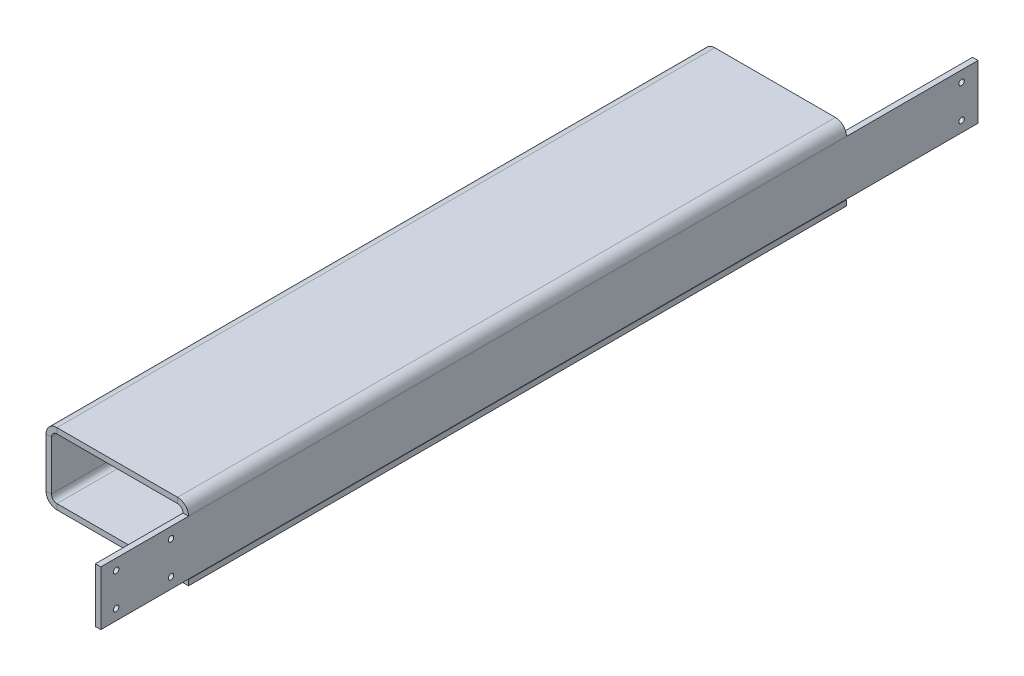
SolidWorks part; units mm, degrees
note: The reader was unsure of these and kept them because the rebuilt part matched: flange length of "Edge-Flange1", "Edge-Flange2", "Edge-Flange3".
ref_plane "Front Plane" through (0, 0, 0) normal (0, 0, 1) x (1, 0, 0)
ref_plane "Top Plane" through (0, 0, 0) normal (0, 1, 0) x (1, 0, 0)
ref_plane "Right Plane" through (0, 0, 0) normal (1, 0, 0) x (0, 0, -1)
sketch "Sketch1" plane through (0, 0, 0) normal (0, 1, 0) x (1, 0, 0)
  line L1 (0, 0) -> (79.375, 0)
  line L2 (0, 0) -> (0, 381)
  line L3 (0, 381) -> (79.375, 381)
  line L4 (79.375, 0) -> (79.375, 381)
  dimension "D1" = 79.375
  dimension "D2" = 381
base flange "Base-Flange1" sketch "Sketch1" thickness 3.175 reverse thickness direction no parameters "D1"=3.175
edge flange "Edge-Flange1" sketch "Sketch8" flange angle 90 flange length 38.1 flange position material outside bend radius 3.175 thickness 3.175 relief rectangular parameters "D6"=10
sketch "Sketch8" plane through (0, 0, 0) normal (-1, 0, 0) x (0, 0, 1)
  line L0 (-381, 0) -> (0, 0) construction
  line L1 (-381, 0) -> (0, 0)
  line L2 (-381, 0) -> (-381, 34.925)
  line L3 (-381, 34.925) -> (0, 34.925)
  line L4 (0, 34.925) -> (0, 0)
bend "EdgeBend1" bend radius 3.175 bend angle 90 parameters "D5"=1
edge flange "Edge-Flange2" sketch "Sketch13" flange angle 90 flange length 79.375 flange position material outside bend radius 3.175 thickness 3.175 relief rectangular parameters "D6"=10
sketch "Sketch13" plane through (0, 34.925, 0) normal (0, 1, 0) x (0, 0, 1)
  line L2 (0, 0) -> (0, 76.2)
  line L3 (0, 76.2) -> (-381, 76.2)
  line L4 (-381, 76.2) -> (-381, 0)
  line L6 (0, 0) -> (-381, 0) construction
  line L7 (0, 0) -> (-381, 0)
bend "EdgeBend2" bend radius 3.175 bend angle 90 parameters "D5"=2
edge flange "Edge-Flange3" sketch "Sketch16" flange angle 90 flange length 37.846 flange position material outside bend radius 3.175 thickness 3.175 relief rectangular parameters "D6"=10
sketch "Sketch16" plane through (76.2, 34.925, 0) normal (1, 0, 0) x (0, 0, 1)
  line L0 (0, 0) -> (-381, 0) construction
  line L1 (0, 0) -> (-381, 0)
  line L2 (-381, 0) -> (-381, 34.671)
  line L3 (-381, 34.671) -> (0, 34.671)
  line L4 (0, 34.671) -> (0, 0)
bend "EdgeBend3" bend radius 3.175 bend angle 90 parameters "D5"=3
sketch "Sketch17" plane through (0, 0, 0) normal (0, 1, 0) x (1, 0, 0)
  line L1 (3.175, 381) -> (76.2, 381)
  line L2 (3.175, 381) -> (3.175, 457.2)
  line L3 (3.175, 457.2) -> (76.2, 457.2)
  line L4 (76.2, 381) -> (76.2, 457.2)
  line L5 (79.375, 381) -> (76.2, 381) construction
  dimension "D1" = 3.175
  dimension "D2" = 76.2
sketch "Sketch20" plane through (0, 0, 0) normal (0, 1, 0) x (1, 0, 0)
  line L0 (76.2, 0) -> (79.375, 0) construction
  line L1 (0, 0) -> (76.2, 0)
  line L2 (0, 0) -> (0, -50.8)
  line L3 (0, -50.8) -> (76.2, -50.8)
  line L4 (76.2, 0) -> (76.2, -50.8)
  line L5 (3.175, 0) -> (79.375, 0) construction
  point P8 (0, 0)
  dimension "D1" = 50.8
  dimension "D2" = 3.175
sketch "Sketch24" plane through (76.2, 0, 0) normal (-1, 0, 0) x (0, 0, 1)
  line L1 (0, 31.75) -> (50.8, 31.75)
  line L2 (0, 31.75) -> (0, 0.254)
  line L3 (0, 0.254) -> (50.8, 0.254)
  line L4 (50.8, 31.75) -> (50.8, 0.254)
  point P5 (0, 0)
  dimension "D1" = 50.8
base flange "Tab3" sketch "Sketch24" thickness 3.175 reverse thickness direction no parameters "D1"=3.175
sketch "Sketch27" plane through (76.2, 0, 0) normal (-1, 0, 0) x (0, 0, 1)
  line L1 (-381, 0.254) -> (-457.2, 0.254)
  line L2 (-381, 0.254) -> (-381, 31.75)
  line L3 (-381, 31.75) -> (-457.2, 31.75)
  line L4 (-457.2, 0.254) -> (-457.2, 31.75)
  point P5 (0, 0)
  dimension "D1" = 76.2
base flange "Tab4" sketch "Sketch27" thickness 3.175 reverse thickness direction no parameters "D1"=3.175
sketch "Sketch30" plane through (76.2, 0, 0) normal (-1, 0, 0) x (0, 0, 1)
  line L0 (50.8, 0.254) -> (50.8, 31.75) construction
  line L1 (10.16, 25.527) -> (41.91, 25.527) construction
  line L2 (10.16, 25.527) -> (10.16, 6.477) construction
  line L3 (10.16, 6.477) -> (41.91, 6.477) construction
  line L4 (41.91, 25.527) -> (41.91, 6.477) construction
  line L6 (41.91, 16.002) -> (50.8, 16.002) construction
  circle A0 centre (10.16, 25.527) radius 1.5875
  circle A1 centre (41.91, 25.527) radius 1.5875
  circle A2 centre (41.91, 6.477) radius 1.5875
  circle A3 centre (10.16, 6.477) radius 1.5875
  dimension "D1" = 3.175
  dimension "D2" = 8.89
  dimension "D4" = 31.75
  dimension "D5" = 19.05
extrude "Cut-Extrude2" cut sketch "Sketch30" against normal through all normal cut yes
sketch "Sketch31" plane through (76.2, 0, 0) normal (-1, 0, 0) x (0, 0, 1)
  line L0 (-447.675, 6.477) -> (-447.675, 25.527) construction
  line L1 (-447.675, 16.002) -> (-457.2, 16.002) construction
  line L2 (-457.2, 31.75) -> (-457.2, 0.254) construction
  circle A0 centre (-447.675, 25.527) radius 1.5875
  circle A1 centre (-447.675, 6.477) radius 1.5875
  dimension "D1" = 3.175
  dimension "D2" = 19.05
  dimension "D3" = 9.525
extrude "Cut-Extrude3" cut sketch "Sketch31" against normal through all normal cut yes
sketch "Bend-Lines1" [suppressed] plane through (0, 0, 0) normal (0, 1, 0) x (1, 0, 0)
sketch "Bounding-Box1" [suppressed] plane through (0, 0, 0) normal (0, 1, 0) x (1, 0, 0)
sheet metal parameters "Sheet-Metal1" thickness 3.175 parameters "D1"=3.175
flat pattern "Flat-Pattern1" [suppressed]
sketch "Bend-Lines2" plane through (0, 0, 0) normal (0, 1, 0) x (1, 0, 0)
sketch3d "Bounding-Box2" [suppressed]
  line L0 (0, 0, 0) -> (0, 381, 0) construction
  line L1 (79.375, 0, 0) -> (79.375, 381, 0) construction
  line L2 (0, 0, 0) -> (79.375, 0, 0) construction
  line L3 (0, 381, 0) -> (79.375, 381, 0) construction
sheet metal parameters "Sheet-Metal2" thickness 3.175 parameters "D1"=3.175
flat pattern "Flat-Pattern1"
sketch "Bend-Lines2" plane through (0, 0, 0) normal (0, 1, 0) x (1, 0, 0)
  line L0 (-0.5655, 381) -> (-0.5655, 0) construction
  line L1 (-0.5655, 381) -> (-0.5655, 0) construction
sketch3d "Bounding-Box2" [suppressed]
  line L0 (-36.0559, 0, 0) -> (-36.0559, 381, 0) construction
  line L1 (79.375, 0, 0) -> (79.375, 381, 0) construction
  line L2 (-36.0559, 0, 0) -> (79.375, 0, 0) construction
  line L3 (-36.0559, 381, 0) -> (79.375, 381, 0) construction
bend of the flat pattern "Flatten-<EdgeBend1>1"
sheet metal parameters "Sheet-Metal3" thickness 3.175 parameters "D1"=3.175
flat pattern "Flat-Pattern1"
sketch "Bend-Lines2" plane through (0, 0, 0) normal (0, 1, 0) x (1, 0, 0)
  line L0 (-0.5655, 381) -> (-0.5655, 0) construction
  line L1 (-0.5655, 381) -> (-0.5655, 0) construction
  line L2 (-36.6214, 381) -> (-36.6214, 0) construction
  line L3 (-36.6214, 381) -> (-36.6214, 0) construction
sketch3d "Bounding-Box2" [suppressed]
  line L0 (-113.3868, 0, 0) -> (-113.3868, 381, 0) construction
  line L1 (79.375, 0, 0) -> (79.375, 381, 0) construction
  line L2 (-113.3868, 0, 0) -> (79.375, 0, 0) construction
  line L3 (-113.3868, 381, 0) -> (79.375, 381, 0) construction
bend of the flat pattern "Flatten-<EdgeBend1>1"
bend of the flat pattern "Flatten-<EdgeBend2>1"
sheet metal parameters "Sheet-Metal4" thickness 3.175 parameters "D1"=3.175
flat pattern "Flat-Pattern1"
sketch "Bend-Lines2" plane through (0, 0, 0) normal (0, 1, 0) x (1, 0, 0)
  line L0 (-0.5655, 381) -> (-0.5655, 0) construction
  line L1 (-0.5655, 381) -> (-0.5655, 0) construction
  line L2 (-36.6214, 381) -> (-36.6214, 0) construction
  line L3 (-36.6214, 381) -> (-36.6214, 0) construction
  line L4 (-113.9523, 381) -> (-113.9523, 0) construction
  line L5 (-113.9523, 381) -> (-113.9523, 0) construction
sketch3d "Bounding-Box2" [suppressed]
  line L0 (-149.1888, 0, 0) -> (-149.1888, 381, 0) construction
  line L1 (79.375, 0, 0) -> (79.375, 381, 0) construction
  line L2 (-149.1888, 0, 0) -> (79.375, 0, 0) construction
  line L3 (-149.1888, 381, 0) -> (79.375, 381, 0) construction
bend of the flat pattern "Flatten-<EdgeBend1>1"
bend of the flat pattern "Flatten-<EdgeBend2>1"
bend of the flat pattern "Flatten-<EdgeBend3>1"
sheet metal parameters "Sheet-Metal8" thickness 3.175 parameters "D1"=3.175
flat pattern "Flat-Pattern8"
sketch "Bend-Lines5" plane through (0, 0, 0) normal (0, 1, 0) x (1, 0, 0)
  line L0 (-113.9523, 381) -> (-113.9523, 0) construction
  line L1 (-36.6214, 381) -> (-36.6214, 0) construction
  line L2 (-0.5655, 381) -> (-0.5655, 0) construction
  line L3 (-113.9523, 381) -> (-113.9523, 0) construction
  line L4 (-36.6214, 381) -> (-36.6214, 0) construction
  line L5 (-0.5655, 381) -> (-0.5655, 0) construction
sketch3d "Bounding-Box5" [suppressed]
  line L0 (-149.1888, -50.8, 0) -> (-149.1888, 381, 0) construction
  line L1 (79.375, -50.8, 0) -> (79.375, 381, 0) construction
  line L2 (-149.1888, -50.8, 0) -> (79.375, -50.8, 0) construction
  line L3 (-149.1888, 381, 0) -> (79.375, 381, 0) construction
bend of the flat pattern "Flatten-<EdgeBend3>4"
bend of the flat pattern "Flatten-<EdgeBend2>4"
bend of the flat pattern "Flatten-<EdgeBend1>4"
sheet metal parameters "Sheet-Metal9" thickness 3.175 parameters "D1"=3.175
flat pattern "Flat-Pattern9"
sketch "Bend-Lines6" plane through (0, 0, 0) normal (0, 1, 0) x (1, 0, 0)
  line L0 (-113.9523, 381) -> (-113.9523, 0) construction
  line L1 (-36.6214, 381) -> (-36.6214, 0) construction
  line L2 (-0.5655, 381) -> (-0.5655, 0) construction
  line L3 (-113.9523, 381) -> (-113.9523, 0) construction
  line L4 (-36.6214, 381) -> (-36.6214, 0) construction
  line L5 (-0.5655, 381) -> (-0.5655, 0) construction
sketch3d "Bounding-Box6" [suppressed]
  line L0 (-149.1888, -50.8, 0) -> (-149.1888, 457.2, 0) construction
  line L1 (79.375, -50.8, 0) -> (79.375, 457.2, 0) construction
  line L2 (-149.1888, -50.8, 0) -> (79.375, -50.8, 0) construction
  line L3 (-149.1888, 457.2, 0) -> (79.375, 457.2, 0) construction
bend of the flat pattern "Flatten-<EdgeBend3>5"
bend of the flat pattern "Flatten-<EdgeBend2>5"
bend of the flat pattern "Flatten-<EdgeBend1>5"
sheet metal parameters "Sheet-Metal10" thickness 3.175 parameters "D1"=3.175
flat pattern "Flat-Pattern9"
sketch "Bend-Lines6" plane through (0, 0, 0) normal (0, 1, 0) x (1, 0, 0)
  line L0 (-113.9523, 381) -> (-113.9523, 0) construction
  line L1 (-36.6214, 381) -> (-36.6214, 0) construction
  line L2 (-0.5655, 381) -> (-0.5655, 0) construction
  line L3 (-113.9523, 381) -> (-113.9523, 0) construction
  line L4 (-36.6214, 381) -> (-36.6214, 0) construction
  line L5 (-0.5655, 381) -> (-0.5655, 0) construction
sketch3d "Bounding-Box6" [suppressed]
  line L0 (-149.1888, -50.8, 0) -> (-149.1888, 457.2, 0) construction
  line L1 (79.375, -50.8, 0) -> (79.375, 457.2, 0) construction
  line L2 (-149.1888, -50.8, 0) -> (79.375, -50.8, 0) construction
  line L3 (-149.1888, 457.2, 0) -> (79.375, 457.2, 0) construction
bend of the flat pattern "Flatten-<EdgeBend3>5"
bend of the flat pattern "Flatten-<EdgeBend2>5"
bend of the flat pattern "Flatten-<EdgeBend1>5"
sheet metal parameters "Sheet-Metal11" thickness 3.175 parameters "D1"=3.175
flat pattern "Flat-Pattern9"
sketch "Bend-Lines6" plane through (0, 0, 0) normal (0, 1, 0) x (1, 0, 0)
  line L0 (-113.9523, 381) -> (-113.9523, 0) construction
  line L1 (-36.6214, 381) -> (-36.6214, 0) construction
  line L2 (-0.5655, 381) -> (-0.5655, 0) construction
  line L3 (-113.9523, 381) -> (-113.9523, 0) construction
  line L4 (-36.6214, 381) -> (-36.6214, 0) construction
  line L5 (-0.5655, 381) -> (-0.5655, 0) construction
sketch3d "Bounding-Box6" [suppressed]
  line L0 (-149.1888, -50.8, 0) -> (-149.1888, 457.2, 0) construction
  line L1 (79.375, -50.8, 0) -> (79.375, 457.2, 0) construction
  line L2 (-149.1888, -50.8, 0) -> (79.375, -50.8, 0) construction
  line L3 (-149.1888, 457.2, 0) -> (79.375, 457.2, 0) construction
bend of the flat pattern "Flatten-<EdgeBend3>5"
bend of the flat pattern "Flatten-<EdgeBend2>5"
bend of the flat pattern "Flatten-<EdgeBend1>5"
